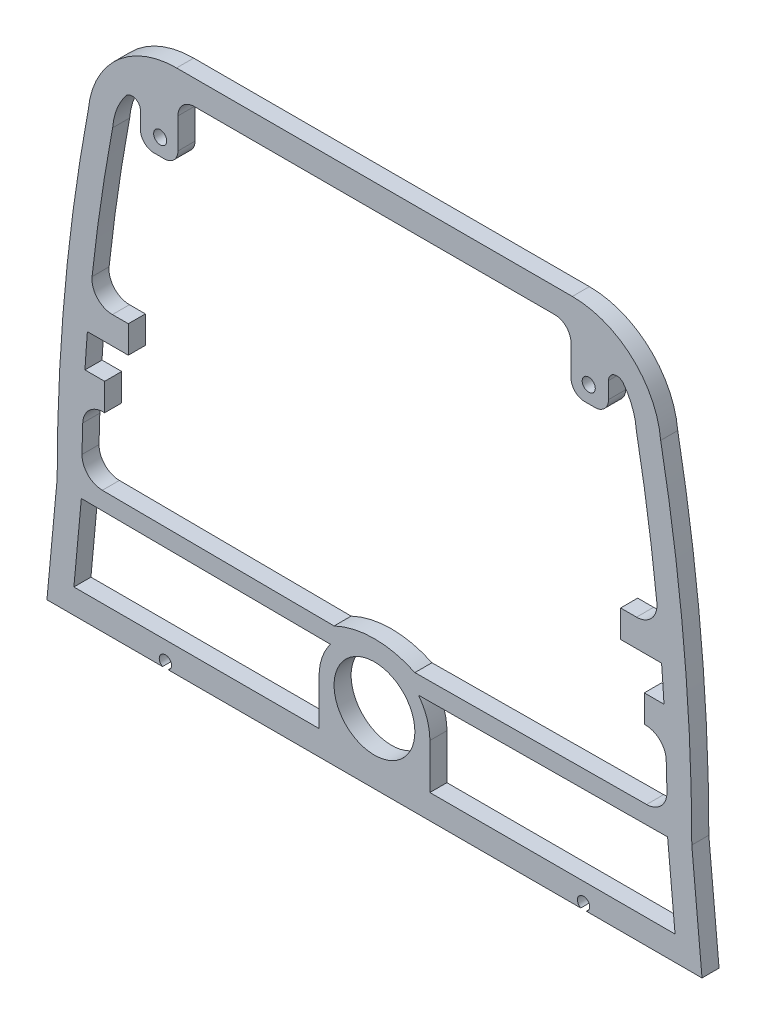
SolidWorks part; units mm, degrees
material "Delrin 2700 NC010, Low Viscosity Acetal Copolymer (SS)"
ref_plane "Front Plane" through (0, 0, 0) normal (0, 0, 1) x (1, 0, 0)
ref_plane "Top Plane" through (0, 0, 0) normal (0, 1, 0) x (1, 0, 0)
ref_plane "Right Plane" through (0, 0, 0) normal (1, 0, 0) x (0, 0, -1)
sketch "Sketch1" plane through (0, 0, 0) normal (0, 0, 1) x (1, 0, 0)
  line L0 (29.5293, -11.9888) -> (30.48, -22.225)
  line L1 (18.415, 26.67) -> (-18.415, 26.67)
  line L2 (-30.48, -22.225) -> (-26.6346, 19.1784) construction
  line L3 (-29.5293, -11.9888) -> (-29.5293, 14.6458) construction
  line L4 (-29.5293, -11.9888) -> (-30.48, -22.225)
  line L5 (18.415, 24.384) -> (-18.415, 24.384)
  line L6 (27.2433, -12.0944) -> (27.9718, -19.939)
  line L7 (-27.9718, -19.939) -> (27.9718, -19.939)
  line L8 (-30.48, -22.225) -> (30.48, -22.225)
  line L9 (-27.2433, -12.0944) -> (-27.9718, -19.939)
  line L10 (18.287, 24.384) -> (18.287, 20.0398)
  line L11 (19.557, 18.7698) -> (20.5126, 18.7698)
  line L12 (21.7826, 20.0398) -> (21.7826, 23.3433)
  line L13 (-18.287, 24.384) -> (-18.287, 20.0398)
  line L14 (-19.557, 18.7698) -> (-20.5126, 18.7698)
  line L15 (-21.7826, 20.0398) -> (-21.7826, 23.3433)
  line L16 (-22.906, 1.27) -> (-26.716, 1.27)
  line L17 (-22.906, 1.27) -> (-22.906, 3.81)
  line L18 (0, 18.415) -> (0, -18.415) construction
  line L19 (-1007.9925, 0) -> (48992.0075, 0) construction
  line L20 (-26.4941, 3.81) -> (-22.906, 3.81)
  line L21 (25.1079, -1.9304) -> (25.1079, -8.382)
  line L22 (-27.0739, -4.4704) -> (-25.1079, -4.4704)
  line L23 (22.906, 1.27) -> (26.716, 1.27)
  line L24 (-26.8155, -2.2098) -> (26.7785, -2.2098) construction
  line L25 (-26.8155, -2.2098) -> (-26.8155, -11.9888) construction
  line L26 (-26.8155, -11.9888) -> (26.8155, -11.9888) construction
  line L27 (26.7785, -2.2098) -> (26.7785, -11.9888) construction
  line L28 (-26.8097, -1.9304) -> (-25.1079, -1.9304)
  line L29 (-19.5453, -1.9304) -> (19.5453, -1.9304)
  line L30 (25.1079, -1.9304) -> (26.8097, -1.9304)
  line L31 (26.94, -1.9304) -> (29.2301, -1.9304) construction
  line L32 (-25.1079, -1.9304) -> (-25.1079, -4.4704)
  line L33 (26.4941, 3.81) -> (22.906, 3.81)
  line L34 (22.906, 1.27) -> (22.906, 3.81)
  line L35 (26.94, -1.9304) -> (25.1079, -1.9304)
  line L36 (-26.94, -1.9304) -> (-25.1079, -1.9304)
  line L37 (27.0739, -4.4704) -> (25.1079, -4.4704)
  line L38 (25.1079, -1.9304) -> (25.1079, -4.4704)
  line L39 (25.1079, -1.9304) -> (25.1079, -8.382) construction
  line L40 (27.2391, -10.8065) -> (3.7592, -10.9728)
  line L41 (3.7592, -10.9728) -> (3.7592, -15.748)
  line L42 (27.277, -12.4573) -> (4.1001, -12.6214)
  line L43 (5.1562, -15.748) -> (5.1562, -19.939)
  line L44 (3.7592, -10.9728) -> (3.7592, -19.939) construction
  line L45 (27.2508, -12.4575) -> (5.4102, -12.6121) construction
  line L46 (-5.1562, -15.748) -> (-5.1562, -19.939)
  line L47 (-3.7592, -10.9728) -> (-3.7592, -15.748)
  line L48 (-27.277, -12.4573) -> (-4.1001, -12.6214)
  line L49 (-27.2391, -10.8065) -> (-3.7592, -10.9728)
  line L50 (5.4102, -12.6121) -> (5.4102, -19.939) construction
  arc A0 (18.415, 26.67) -> (26.6346, 19.1784) centre (18.415, 18.415) cw
  arc A1 (-18.415, 26.67) -> (-26.6346, 19.1784) centre (-18.415, 18.415) ccw
  arc A2 (29.5293, -11.9888) -> (26.6346, 19.1784) centre (-139.7077, -11.9888) ccw
  circle A3 centre (0, -15.748) radius 3.7592
  circle A4 centre (19.4575, -21.717) radius 0.5715
  arc A5 (-29.5293, -11.9888) -> (-26.6346, 19.1784) centre (139.7077, -11.9888) cw
  arc A6 (-27.2433, -12.0944) -> (-24.3667, 18.8696) centre (139.7077, -11.9888) cw
  arc A7 (3.7592, -10.9728) -> (-3.7592, -10.9728) centre (0, -18.8343) ccw
  arc A8 (20.5126, 18.7698) -> (21.7826, 20.0398) centre (20.5126, 20.0398) ccw
  circle A9 centre (-19.939, 20.32) radius 0.6096
  circle A10 centre (19.939, 20.32) radius 0.6096
  arc A11 (18.287, 20.0398) -> (19.557, 18.7698) centre (19.557, 20.0398) ccw
  circle A12 centre (-19.4575, -21.717) radius 0.5715
  arc A13 (18.287, 22.8707) -> (16.7737, 24.384) centre (16.7737, 22.8707) ccw
  arc A14 (23.1564, 22.041) -> (21.7826, 21.5759) centre (22.5482, 21.5759) ccw
  arc A15 (-18.287, 22.8707) -> (-16.7737, 24.384) centre (-16.7737, 22.8707) cw
  arc A16 (-18.287, 20.0398) -> (-19.557, 18.7698) centre (-19.557, 20.0398) cw
  arc A17 (-20.5126, 18.7698) -> (-21.7826, 20.0398) centre (-20.5126, 20.0398) cw
  arc A18 (-18.415, 24.384) -> (-24.3667, 18.8696) centre (-18.415, 18.415) ccw
  arc A19 (18.415, 24.384) -> (24.3667, 18.8696) centre (18.415, 18.415) cw
  arc A20 (27.2433, -12.0944) -> (24.3667, 18.8696) centre (-139.7077, -11.9888) ccw
  arc A21 (-23.1564, 22.041) -> (-21.7826, 21.5759) centre (-22.5482, 21.5759) cw
  arc A22 (-5.1562, -15.748) -> (-4.1001, -12.6214) centre (0, -15.748) cw
  arc A24 (5.1562, -15.748) -> (4.1001, -12.6214) centre (0, -15.748) ccw
  point P0 (0, 0)
  point P1 (0, 26.67)
  point P26 (0, -22.225)
  point P31 (0, -11.9888)
  dimension "D4" = 2.286
  dimension "D6" = 8.255
  dimension "D7" = 19.4575
  dimension "D8" = 48.895
  dimension "D9" = 15.748
  dimension "D5" = 1.2192
  dimension "D17" = 1.143
  dimension "D3" = 7.5184
  dimension "D18" = 1.27
  dimension "D19" = 1.27
  dimension "D26" = 1.397
  dimension "D2" = 36.83
  dimension "D10" = 21.717
  dimension "D11" = 20.32
  dimension "D12" = 60.96
  dimension "D13" = 19.939
  dimension "D14" = 22.225
  dimension "D15" = 53.594
  dimension "D16" = 9.779
  dimension "D20" = 2.54
  dimension "D21" = 3.81
  dimension "D22" = 2.54
  dimension "D23" = 3.2004
  dimension "D24" = 1.016
  dimension "D25" = 1.651
extrude "Boss-Extrude1" add sketch "Sketch1" along normal blind 1.5875 contours L8 A12 A4 L0 A2 A0 L1 A1 A5 L4 A20 L6 L7 L9 A6 A18 L5 A19 | L5 A18 A9 | A19 L5 A10 | L13 A15 L5 | A18 A21 L15 | A13 L10 L5 | A19 L12 A14 | A20 L33 L34 | L37 A20 L35 L38 | A6 L22 L32 L36 | A6 L16 L17 L20 | L6 A20 L40 L41 A3 L47 L49 A6 L9 A22 L7 L42 | L41 A7 L47 A3 region at (29.2265, -17.1792, 0) region at (19.9793, 21.6011, 0) region at (17.949, 24.046, 0) region at (22.1557, 22.5932, 0) region at (-17.949, 24.046, 0) region at (-19.9793, 21.6011, 0) region at (24.7577, 2.5273, 0) region at (-22.1557, 22.5932, 0) region at (26.0595, -3.2153, 0) region at (26.6893, -11.4522, 0) region at (-24.7577, 2.5273, 0) region at (0, -11.7307, 0) region at (-26.0595, -3.2153, 0)
ref_axis "Axis1" through (0, -15.748, 0) along (0, 0, 1)
fillet "Fillet1" radius 1.905 6 edges at (26.4941, 3.81, 0.7937) (-27.2391, -10.8065, 0.7937) (-27.0739, -4.4704, 0.7937) (-26.4941, 3.81, 0.7937) (27.2391, -10.8065, 0.7937) (27.0739, -4.4704, 0.7937)
